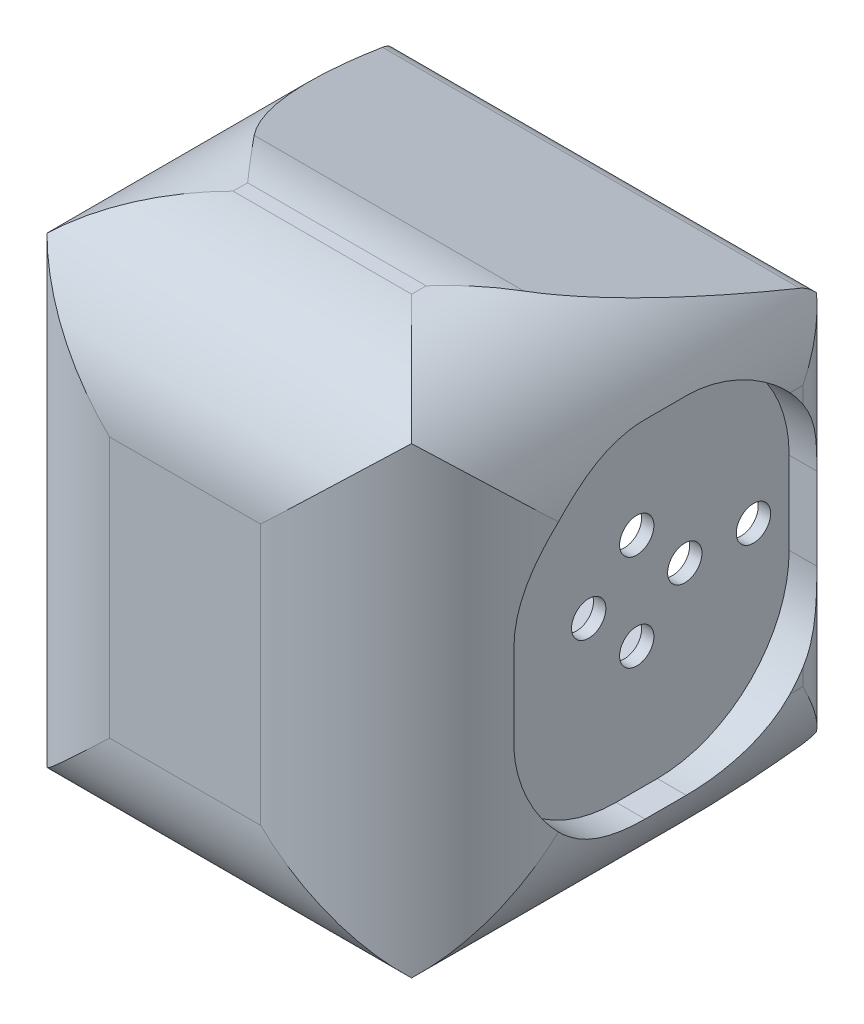
SolidWorks part; units mm, degrees
ref_plane "Front Plane" through (0, 0, 0) normal (0, 0, 1) x (1, 0, 0)
ref_plane "Top Plane" through (0, 0, 0) normal (0, 1, 0) x (1, 0, 0)
ref_plane "Right Plane" through (0, 0, 0) normal (1, 0, 0) x (0, 0, -1)
ref_plane "PX_m33_000" through (-33, 0, 0) normal (1, 0, 0) x (0, 0, -1)
sketch "S_prism1" plane through (-33, 0, 0) normal (1, 0, 0) x (0, 0, -1)
  line L0 (0, -25.0397) -> (0, 25.0397)
  line L1 (-2.8311, 28.8651) -> (-32.2859, 37.8651)
  line L2 (-39.8836, 39) -> (-42, 39)
  line L3 (-62, 19) -> (-62, -19)
  line L4 (-42, -39) -> (-39.8836, -39)
  line L5 (-32.2859, -37.8651) -> (-2.8311, -28.8651)
  arc A0 (-2.8311, -28.8651) -> (0, -25.0397) centre (-4.0002, -25.0395) ccw
  arc A1 (0, 25.0397) -> (-2.8311, 28.8651) centre (-4.0002, 25.0395) ccw
  arc A2 (-32.2859, 37.8651) -> (-39.8836, 39) centre (-39.8837, 12.9999) ccw
  arc A3 (-42, 39) -> (-62, 19) centre (-41.9999, 18.9999) ccw
  arc A4 (-62, -19) -> (-42, -39) centre (-41.9999, -18.9999) ccw
  arc A5 (-39.8836, -39) -> (-32.2859, -37.8651) centre (-39.8837, -12.9999) ccw
extrude "Boss_1" add sketch "S_prism1" along normal blind 66
ref_plane "PX_p27_750" through (27.75, 0, 0) normal (1, 0, 0) x (0, 0, -1)
sketch "S_prism2" plane through (27.75, 0, 0) normal (1, 0, 0) x (0, 0, -1)
  line L0 (-12.2, -6) -> (-12.2, 6)
  line L1 (-21, 14.8) -> (-27, 14.8)
  line L2 (-35.8, 6) -> (-35.8, -6)
  line L3 (-27, -14.8) -> (-21, -14.8)
  arc A0 (-21, -14.8) -> (-12.2, -6) centre (-21.0001, -5.9999) ccw
  arc A1 (-12.2, 6) -> (-21, 14.8) centre (-21.0001, 5.9999) ccw
  arc A2 (-27, 14.8) -> (-35.8, 6) centre (-26.9999, 5.9999) ccw
  arc A3 (-35.8, -6) -> (-27, -14.8) centre (-26.9999, -5.9999) ccw
extrude "Boss_2" add sketch "S_prism2" along normal blind 5.25
ref_plane "PY_m40_000" through (0, -40, 0) normal (0, 1, 0) x (1, 0, 0)
sketch "S_pcut3" plane through (0, -40, 0) normal (0, 1, 0) x (1, 0, 0)
  line L0 (33.6, -62.6) -> (11, -62.6)
  line L1 (11, -62.6) -> (11, -62)
  line L2 (33, -40) -> (33.6, -40)
  line L3 (33.6, -40) -> (33.6, -62.6)
  arc A0 (11, -62) -> (33, -40) centre (10.9998, -39.9998) ccw
extrude "Cut_3" cut sketch "S_pcut3" along normal blind 80
sketch "S_pcut4" plane through (0, -40, 0) normal (0, 1, 0) x (1, 0, 0)
  line L0 (-33.6, -62.6) -> (-11, -62.6)
  line L1 (-11, -62.6) -> (-11, -62)
  line L2 (-33, -40) -> (-33.6, -40)
  line L3 (-33.6, -40) -> (-33.6, -62.6)
  arc A0 (-11, -62) -> (-33, -40) centre (-10.9998, -39.9998) cw
extrude "Cut_4" cut sketch "S_pcut4" along normal blind 80
sketch "S_pcut5" plane through (0, -40, 0) normal (0, 1, 0) x (1, 0, 0)
  line L0 (33.6, 0.6) -> (28, 0.6)
  line L1 (28, 0.6) -> (28, 0)
  line L2 (33, -5) -> (33.6, -5)
  line L3 (33.6, -5) -> (33.6, 0.6)
  arc A0 (28, 0) -> (33, -5) centre (27.9999, -5.0001) cw
extrude "Cut_5" cut sketch "S_pcut5" along normal blind 80
sketch "S_pcut6" plane through (0, -40, 0) normal (0, 1, 0) x (1, 0, 0)
  line L0 (-33.6, 0.6) -> (-28, 0.6)
  line L1 (-28, 0.6) -> (-28, 0)
  line L2 (-33, -5) -> (-33.6, -5)
  line L3 (-33.6, -5) -> (-33.6, 0.6)
  arc A0 (-28, 0) -> (-33, -5) centre (-27.9999, -5.0001) ccw
extrude "Cut_6" cut sketch "S_pcut6" along normal blind 80
ref_plane "PZ_m0_100" through (0, 0, -0.1) normal (0, 0, 1) x (1, 0, 0)
sketch "S_pcut7" plane through (0, 0, -0.1) normal (0, 0, 1) x (1, 0, 0)
  line L0 (33.6, 39.6) -> (13, 39.6)
  line L1 (13, 39.6) -> (13, 39)
  line L2 (33, 19) -> (33.6, 19)
  line L3 (33.6, 19) -> (33.6, 39.6)
  arc A0 (13, 39) -> (33, 19) centre (12.9999, 18.9999) cw
extrude "Cut_7" cut sketch "S_pcut7" along normal blind 62.2
sketch "S_pcut8" plane through (0, 0, -0.1) normal (0, 0, 1) x (1, 0, 0)
  line L0 (33.6, -39.6) -> (13, -39.6)
  line L1 (13, -39.6) -> (13, -39)
  line L2 (33, -19) -> (33.6, -19)
  line L3 (33.6, -19) -> (33.6, -39.6)
  arc A0 (13, -39) -> (33, -19) centre (12.9999, -18.9999) ccw
extrude "Cut_8" cut sketch "S_pcut8" along normal blind 62.2
sketch "S_pcut9" plane through (0, 0, -0.1) normal (0, 0, 1) x (1, 0, 0)
  line L0 (-33.6, 39.6) -> (-13, 39.6)
  line L1 (-13, 39.6) -> (-13, 39)
  line L2 (-33, 19) -> (-33.6, 19)
  line L3 (-33.6, 19) -> (-33.6, 39.6)
  arc A0 (-13, 39) -> (-33, 19) centre (-12.9999, 18.9999) ccw
extrude "Cut_9" cut sketch "S_pcut9" along normal blind 62.2
sketch "S_pcut10" plane through (0, 0, -0.1) normal (0, 0, 1) x (1, 0, 0)
  line L0 (-33.6, -39.6) -> (-13, -39.6)
  line L1 (-13, -39.6) -> (-13, -39)
  line L2 (-33, -19) -> (-33.6, -19)
  line L3 (-33.6, -19) -> (-33.6, -39.6)
  arc A0 (-13, -39) -> (-33, -19) centre (-12.9999, -18.9999) cw
extrude "Cut_10" cut sketch "S_pcut10" along normal blind 62.2
ref_plane "PX_p27_800" through (27.8, 0, 0) normal (1, 0, 0) x (0, 0, -1)
sketch "S_pcut11" plane through (27.8, 0, 0) normal (1, 0, 0) x (0, 0, -1)
  line L0 (-1.8, -6) -> (-1.8, 6)
  line L1 (-21, 25.2) -> (-27, 25.2)
  line L2 (-46.2, 6) -> (-46.2, -6)
  line L3 (-27, -25.2) -> (-21, -25.2)
  arc A0 (-21, -25.2) -> (-1.8, -6) centre (-20.9998, -6.0002) ccw
  arc A1 (-1.8, 6) -> (-21, 25.2) centre (-20.9998, 6.0002) ccw
  arc A2 (-27, 25.2) -> (-46.2, 6) centre (-27.0002, 6.0002) ccw
  arc A3 (-46.2, -6) -> (-27, -25.2) centre (-27.0002, -6.0002) ccw
extrude "Cut_11" cut sketch "S_pcut11" along normal blind 6.2
ref_plane "PX_p25_900" through (25.9, 0, 0) normal (1, 0, 0) x (0, 0, -1)
sketch "S_hole12" plane through (25.9, 0, 0) normal (1, 0, 0) x (0, 0, -1)
  circle A0 centre (-7, 0) radius 2.5
  dimension "D1_S_hole12" = 5
  dimension "P2" = 7
extrude "Hole_12" cut sketch "S_hole12" along normal blind 2
sketch "S_cut13" plane through (0, 0, -0.1) normal (0, 0, 1) x (1, 0, 0)
  line L0 (-26, -24) -> (26, -24)
  line L1 (26, -24) -> (26, 24)
  line L2 (26, 24) -> (-26, 24)
  line L3 (-26, 24) -> (-26, -24)
  dimension "P1" = 26
  dimension "P2" = 24
  dimension "P3" = 26
  dimension "P4" = 24
  dimension "P5" = 26
  dimension "P6" = 24
  dimension "P7" = 26
  dimension "P8" = 24
extrude "Pocket_13" cut sketch "S_cut13" along normal blind 16.2
ref_plane "PZ_p16_000" through (0, 0, 16) normal (0, 0, 1) x (1, 0, 0)
sketch "S_cut14" plane through (0, 0, 16) normal (0, 0, 1) x (1, 0, 0)
  line L0 (-26, -30) -> (26, -30)
  line L1 (26, -30) -> (26, 30)
  line L2 (26, 30) -> (-26, 30)
  line L3 (-26, 30) -> (-26, -30)
  dimension "P1" = 26
  dimension "P2" = 30
  dimension "P3" = 26
  dimension "P4" = 30
  dimension "P5" = 26
  dimension "P6" = 30
  dimension "P7" = 26
  dimension "P8" = 30
extrude "Pocket_14" cut sketch "S_cut14" along normal blind 36
ref_plane "PZ_p51_900" through (0, 0, 51.9) normal (0, 0, 1) x (1, 0, 0)
sketch "S_cut15" plane through (0, 0, 51.9) normal (0, 0, 1) x (1, 0, 0)
  line L0 (-18, -24) -> (18, -24)
  line L1 (18, -24) -> (18, 24)
  line L2 (18, 24) -> (-18, 24)
  line L3 (-18, 24) -> (-18, -24)
  dimension "P1" = 18
  dimension "P2" = 24
  dimension "P3" = 18
  dimension "P4" = 24
  dimension "P5" = 18
  dimension "P6" = 24
  dimension "P7" = 18
  dimension "P8" = 24
extrude "Pocket_15" cut sketch "S_cut15" along normal blind 6.1
sketch "S_cut16" plane through (0, 0, 16) normal (0, 0, 1) x (1, 0, 0)
  line L0 (-33.1, -16) -> (-25.9, -16)
  line L1 (-25.9, -16) -> (-25.9, 16)
  line L2 (-25.9, 16) -> (-33.1, 16)
  line L3 (-33.1, 16) -> (-33.1, -16)
  dimension "P1" = 33.1
  dimension "P2" = 16
  dimension "P3" = 25.9
  dimension "P4" = 16
  dimension "P5" = 25.9
  dimension "P6" = 16
  dimension "P7" = 33.1
  dimension "P8" = 16
extrude "Pocket_16" cut sketch "S_cut16" along normal blind 28
sketch "S_hole17" plane through (25.9, 0, 0) normal (1, 0, 0) x (0, 0, -1)
  circle A0 centre (-31, 0) radius 2.5
  dimension "D1_S_hole17" = 5
  dimension "P2" = 31
extrude "Hole_17" cut sketch "S_hole17" along normal blind 7.2
sketch "S_hole18" plane through (25.9, 0, 0) normal (1, 0, 0) x (0, 0, -1)
  circle A0 centre (-24, 7) radius 2.5
  dimension "D1_S_hole18" = 5
  dimension "P2" = 24
  dimension "P3" = 7
extrude "Hole_18" cut sketch "S_hole18" along normal blind 7.2
sketch "S_hole19" plane through (25.9, 0, 0) normal (1, 0, 0) x (0, 0, -1)
  circle A0 centre (-24, -7) radius 2.5
  dimension "D1_S_hole19" = 5
  dimension "P2" = 24
  dimension "P3" = 7
extrude "Hole_19" cut sketch "S_hole19" along normal blind 7.2
sketch "S_hole20" plane through (25.9, 0, 0) normal (1, 0, 0) x (0, 0, -1)
  circle A0 centre (-17, 0) radius 2.5
  dimension "D1_S_hole20" = 5
  dimension "P2" = 17
extrude "Hole_20" cut sketch "S_hole20" along normal blind 7.2
ref_plane "PX_m33_100" through (-33.1, 0, 0) normal (1, 0, 0) x (0, 0, -1)
sketch "S_hole21" plane through (-33.1, 0, 0) normal (1, 0, 0) x (0, 0, -1)
  circle A0 centre (-8, -10) radius 1.2
  dimension "D1_S_hole21" = 2.4
  dimension "P2" = 8
  dimension "P3" = 10
extrude "Hole_21" cut sketch "S_hole21" along normal blind 7.2
sketch "S_hole22" plane through (-33.1, 0, 0) normal (1, 0, 0) x (0, 0, -1)
  circle A0 centre (-8, -10) radius 2.3
  dimension "D1_S_hole22" = 4.6
  dimension "P2" = 8
  dimension "P3" = 10
extrude "Hole_22" cut sketch "S_hole22" along normal blind 2
sketch "S_hole23" plane through (-33.1, 0, 0) normal (1, 0, 0) x (0, 0, -1)
  circle A0 centre (-8, 10) radius 1.2
  dimension "D1_S_hole23" = 2.4
  dimension "P2" = 8
  dimension "P3" = 10
extrude "Hole_23" cut sketch "S_hole23" along normal blind 7.2
sketch "S_hole24" plane through (-33.1, 0, 0) normal (1, 0, 0) x (0, 0, -1)
  circle A0 centre (-8, 10) radius 2.3
  dimension "D1_S_hole24" = 4.6
  dimension "P2" = 8
  dimension "P3" = 10
extrude "Hole_24" cut sketch "S_hole24" along normal blind 2
equation "\"plate_t\" = 3"
equation "\"clearance\" = 0.5"
